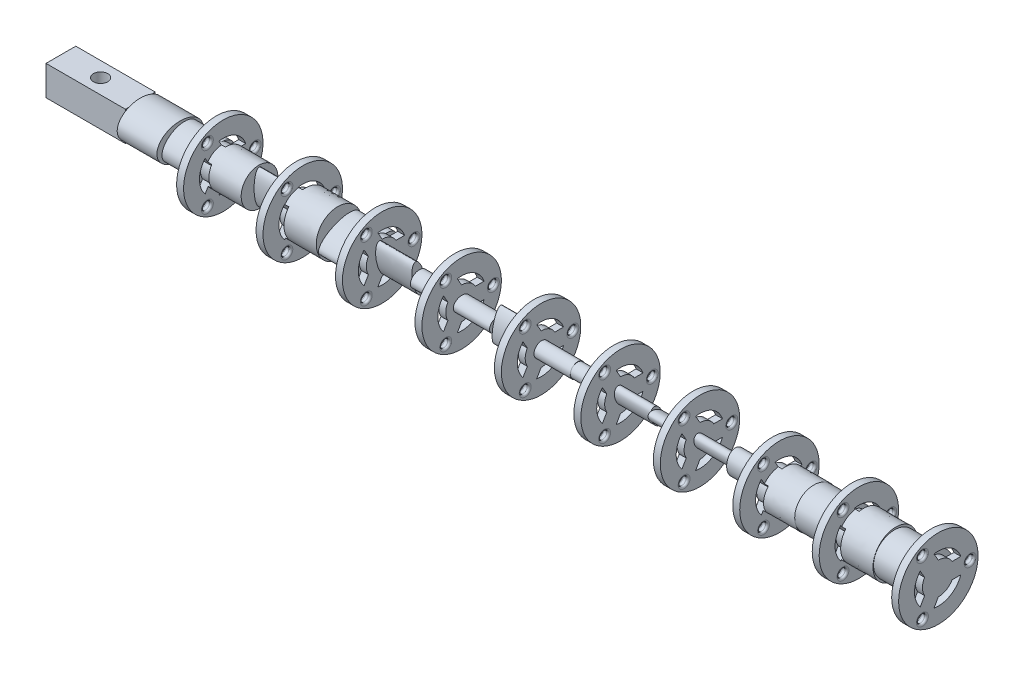
SolidWorks part; units mm, degrees
ref_plane "Front Plane" through (0, 0, 0) normal (0, 0, 1) x (1, 0, 0)
ref_plane "Top Plane" through (0, 0, 0) normal (0, 1, 0) x (1, 0, 0)
ref_plane "Right Plane" through (0, 0, 0) normal (1, 0, 0) x (0, 0, -1)
sketch "Sketch28" plane through (0, 0, 0) normal (1, 0, 0) x (0, 0, -1)
  line L0 (0, 0) -> (0, 30) construction
  line L1 (0, 0) -> (-30, 0) construction
  line L2 (19.0774, 0) -> (-19.0774, 0) construction
  dimension "D1" = 30
sketch "Sketch1" plane through (0, 0, 0) normal (1, 0, 0) x (0, 0, -1)
  line L0 (0, 4.3212) -> (0, 0) construction
  line L1 (0, 0) -> (-5.8276, 0) construction
  line L2 (0, 0) -> (0, 30) construction
  ellipse E0 centre (0, 0) end of major axis (-5.8276, 0) minor radius 4.3212
  dimension "ry_1" = 4.3212
  dimension "rz_1" = 5.8276
  dimension "phi_1" = 0
extrude "Boss-Extrude1" add sketch "Sketch1" along normal blind 10
ref_plane "Plane1" through (10, 0, 0) normal (1, 0, 0) x (0, 0, -1)
sketch "Sketch2" plane through (10, 0, 0) normal (1, 0, 0) x (0, 0, -1)
  line L0 (0, 0) -> (-1.4016, 3.0904) construction
  line L1 (0, 0) -> (-4.3308, -1.9641) construction
  line L3 (0, 0) -> (0, 30) construction
  ellipse E0 centre (0, 0) end of major axis (4.3308, 1.9641) minor radius 3.3934
  dimension "phi_2" = 24.395
  dimension "ry_2" = 3.3934
  dimension "rz_2" = 4.7554
extrude "Boss-Extrude2" add sketch "Sketch2" along normal blind 10
ref_plane "Plane2" through (20, 0, 0) normal (1, 0, 0) x (0, 0, -1)
sketch "Sketch3" plane through (20, 0, 0) normal (1, 0, 0) x (0, 0, -1)
  line L0 (0, 0) -> (-2.0467, 4.3518) construction
  line L1 (0, 0) -> (-4.1465, -1.9502) construction
  line L2 (0, 0) -> (0, 30) construction
  ellipse E0 centre (0, 0) end of major axis (-2.0467, 4.3518) minor radius 4.5822
  dimension "ry_3" = 4.809
  dimension "rz_3" = 4.5822
  dimension "phi_3" = 25.188
extrude "Boss-Extrude3" add sketch "Sketch3" along normal blind 10
ref_plane "Plane3" through (30, 0, 0) normal (1, 0, 0) x (0, 0, -1)
sketch "Sketch4" plane through (30, 0, 0) normal (1, 0, 0) x (0, 0, -1)
  line L0 (-0.0912, 4.3279) -> (0, 0) construction
  line L1 (0, 0) -> (-1.3721, -0.0289) construction
  line L2 (0, 0) -> (0, 30) construction
  ellipse E0 centre (0, 0) end of major axis (0.0912, -4.3279) minor radius 1.3724
  dimension "ry_4" = 4.3289
  dimension "rz_4" = 1.3724
  dimension "phi_4" = 1.207
extrude "Boss-Extrude4" add sketch "Sketch4" along normal blind 10
ref_plane "Plane4" through (40, 0, 0) normal (1, 0, 0) x (0, 0, -1)
sketch "Sketch5" plane through (40, 0, 0) normal (1, 0, 0) x (0, 0, -1)
  line L0 (-3.5013, 4.7623) -> (0, 0) construction
  line L1 (0, 0) -> (-4.5221, -3.3247) construction
  line L2 (0, 0) -> (0, 30) construction
  ellipse E0 centre (0, 0) end of major axis (-3.5013, 4.7623) minor radius 5.6128
  dimension "ry_5" = 5.9109
  dimension "rz_5" = 5.6128
  dimension "phi_5" = 36.324
extrude "Boss-Extrude5" add sketch "Sketch5" along normal blind 10
ref_plane "Plane5" through (50, 0, 0) normal (1, 0, 0) x (0, 0, -1)
sketch "Sketch6" plane through (50, 0, 0) normal (1, 0, 0) x (0, 0, -1)
  line L0 (-0.9096, 2.2618) -> (0, 0) construction
  line L1 (0, 0) -> (-5.0808, -2.0433) construction
  line L2 (0, 0) -> (0, 30) construction
  ellipse E0 centre (0, 0) end of major axis (-5.0808, -2.0433) minor radius 2.4378
  dimension "ry_6" = 2.4378
  dimension "rz_6" = 5.4763
  dimension "phi_6" = 21.908
extrude "Boss-Extrude6" add sketch "Sketch6" along normal blind 10
ref_plane "Plane6" through (60, 0, 0) normal (1, 0, 0) x (0, 0, -1)
sketch "Sketch7" plane through (60, 0, 0) normal (1, 0, 0) x (0, 0, -1)
  line L0 (-0.8479, 3.9653) -> (0, 0) construction
  line L1 (0, 0) -> (-1.4136, -0.3023) construction
  line L2 (0, 0) -> (0, 30) construction
  ellipse E0 centre (0, 0) end of major axis (0.8479, -3.9653) minor radius 1.4456
  dimension "ry_7" = 4.0549
  dimension "rz_7" = 1.4456
  dimension "phi_7" = 12.069
extrude "Boss-Extrude7" add sketch "Sketch7" along normal blind 10
ref_plane "Plane7" through (70, 0, 0) normal (1, 0, 0) x (0, 0, -1)
sketch "Sketch8" plane through (70, 0, 0) normal (1, 0, 0) x (0, 0, -1)
  line L0 (-0.6185, 1.5939) -> (0, 0) construction
  line L1 (0, 0) -> (-1.9484, -0.756) construction
  line L2 (0, 0) -> (0, 30) construction
  ellipse E0 centre (0, 0) end of major axis (-1.9484, -0.756) minor radius 1.7097
  dimension "ry_8" = 1.7097
  dimension "rz_8" = 2.09
  dimension "phi_8" = 21.207
extrude "Boss-Extrude8" add sketch "Sketch8" along normal blind 10
ref_plane "Plane8" through (80, 0, 0) normal (1, 0, 0) x (0, 0, -1)
sketch "Sketch9" plane through (80, 0, 0) normal (1, 0, 0) x (0, 0, -1)
  line L0 (-0.1773, 1.7176) -> (0, 0) construction
  line L1 (0, 0) -> (-2.0864, -0.2153) construction
  line L2 (0, 0) -> (0, 30) construction
  ellipse E0 centre (0, 0) end of major axis (2.0864, 0.2153) minor radius 1.7267
  dimension "ry_9" = 1.7267
  dimension "rz_9" = 2.0974
  dimension "phi_9" = 5.893
extrude "Boss-Extrude9" add sketch "Sketch9" along normal blind 10
ref_plane "Plane9" through (90, 0, 0) normal (1, 0, 0) x (0, 0, -1)
sketch "Sketch10" plane through (90, 0, 0) normal (1, 0, 0) x (0, 0, -1)
  line L0 (-1.2148, 0.2533) -> (0, 0) construction
  line L1 (0, 0) -> (-0.7981, -3.8268) construction
  line L2 (0, 0) -> (0, 30) construction
  ellipse E0 centre (0, 0) end of major axis (-0.7981, -3.8268) minor radius 1.2409
  dimension "ry_10" = 1.2409
  dimension "rz_10" = 3.9091
  dimension "phi_10" = 78.22
extrude "Boss-Extrude10" add sketch "Sketch10" along normal blind 10
ref_plane "Plane10" through (100, 0, 0) normal (1, 0, 0) x (0, 0, -1)
sketch "Sketch11" plane through (100, 0, 0) normal (1, 0, 0) x (0, 0, -1)
  line L0 (-1.2809, 1.1559) -> (0, 0) construction
  line L1 (0, 0) -> (-1.2502, -1.3855) construction
  line L2 (0, 0) -> (0, 30) construction
  ellipse E0 centre (0, 0) end of major axis (-1.2502, -1.3855) minor radius 1.7253
  dimension "ry_11" = 1.7253
  dimension "rz_11" = 1.8662
  dimension "phi_11" = 47.938
extrude "Boss-Extrude11" add sketch "Sketch11" along normal blind 10
ref_plane "Plane11" through (110, 0, 0) normal (1, 0, 0) x (0, 0, -1)
sketch "Sketch12" plane through (110, 0, 0) normal (1, 0, 0) x (0, 0, -1)
  line L0 (-0.4519, 1.6644) -> (0, 0) construction
  line L1 (0, 0) -> (-1.7077, -0.4637) construction
  line L2 (0, 0) -> (0, 30) construction
  ellipse E0 centre (0, 0) end of major axis (1.7077, 0.4637) minor radius 1.7246
  dimension "ry_12" = 1.7246
  dimension "rz_12" = 1.7695
  dimension "phi_12" = 15.191
extrude "Boss-Extrude12" add sketch "Sketch12" along normal blind 10
ref_plane "Plane12" through (120, 0, 0) normal (1, 0, 0) x (0, 0, -1)
sketch "Sketch13" plane through (120, 0, 0) normal (1, 0, 0) x (0, 0, -1)
  line L0 (-0.9033, 2.292) -> (0, 0) construction
  line L1 (0, 0) -> (-1.2574, -0.4956) construction
  line L2 (0, 0) -> (0, 30) construction
  ellipse E0 centre (0, 0) end of major axis (-0.9033, 2.292) minor radius 1.3515
  dimension "ry_13" = 2.4636
  dimension "rz_13" = 1.3515
  dimension "phi_13" = 21.51
extrude "Boss-Extrude13" add sketch "Sketch13" along normal blind 10
ref_plane "Plane13" through (130, 0, 0) normal (1, 0, 0) x (0, 0, -1)
sketch "Sketch14" plane through (130, 0, 0) normal (1, 0, 0) x (0, 0, -1)
  line L0 (-2.0836, 1.3795) -> (0, 0) construction
  line L1 (0, 0) -> (-0.7042, -1.0636) construction
  line L2 (0, 0) -> (0, 30) construction
  ellipse E0 centre (0, 0) end of major axis (-2.0836, 1.3795) minor radius 1.2756
  dimension "ry_14" = 2.4989
  dimension "rz_14" = 1.2756
  dimension "phi_14" = 56.493
extrude "Boss-Extrude14" add sketch "Sketch14" along normal blind 10
ref_plane "Plane14" through (140, 0, 0) normal (1, 0, 0) x (0, 0, -1)
sketch "Sketch15" plane through (140, 0, 0) normal (1, 0, 0) x (0, 0, -1)
  line L0 (-1.0514, 1.824) -> (0, 0) construction
  line L1 (0, 0) -> (-1.1024, -0.6354) construction
  line L2 (0, 0) -> (0, 30) construction
  ellipse E0 centre (0, 0) end of major axis (1.0514, -1.824) minor radius 1.2724
  dimension "ry_15" = 2.1053
  dimension "rz_15" = 1.2724
  dimension "phi_15" = 29.96
extrude "Boss-Extrude15" add sketch "Sketch15" along normal blind 10
ref_plane "Plane15" through (150, 0, 0) normal (1, 0, 0) x (0, 0, -1)
sketch "Sketch16" plane through (150, 0, 0) normal (1, 0, 0) x (0, 0, -1)
  line L0 (-0.5018, 3.1443) -> (0, 0) construction
  line L1 (0, 0) -> (-2.3641, -0.3773) construction
  line L3 (0, 0) -> (0, 30) construction
  ellipse E0 centre (0, 0) end of major axis (0.5018, -3.1443) minor radius 2.394
  dimension "ry_16" = 3.1841
  dimension "rz_16" = 2.394
  dimension "phi_16" = 9.067
extrude "Boss-Extrude16" add sketch "Sketch16" along normal blind 10
ref_plane "Plane16" through (160, 0, 0) normal (1, 0, 0) x (0, 0, -1)
sketch "Sketch17" plane through (160, 0, 0) normal (1, 0, 0) x (0, 0, -1)
  line L0 (-2.0662, 3.9425) -> (0, 0) construction
  line L1 (0, 0) -> (-4.5704, -2.3953) construction
  line L2 (0, 0) -> (0, 30) construction
  ellipse E0 centre (0, 0) end of major axis (4.5704, 2.3953) minor radius 4.4511
  dimension "ry_17" = 4.4511
  dimension "rz_17" = 5.16
  dimension "phi_17" = 27.658
extrude "Boss-Extrude17" add sketch "Sketch17" along normal blind 10
ref_plane "Plane17" through (170, 0, 0) normal (1, 0, 0) x (0, 0, -1)
sketch "Sketch18" plane through (170, 0, 0) normal (1, 0, 0) x (0, 0, -1)
  line L0 (-4.1845, 3.5234) -> (0, 0) construction
  line L1 (0, 0) -> (-3.2226, -3.8272) construction
  line L2 (0, 0) -> (0, 30) construction
  ellipse E0 centre (0, 0) end of major axis (4.1845, -3.5234) minor radius 5.0033
  dimension "ry_18" = 5.4703
  dimension "rz_18" = 5.0033
  dimension "phi_18" = 49.902
extrude "Boss-Extrude18" add sketch "Sketch18" along normal blind 10
ref_plane "Plane18" through (180, 0, 0) normal (1, 0, 0) x (0, 0, -1)
sketch "Sketch19" plane through (180, 0, 0) normal (1, 0, 0) x (0, 0, -1)
  line L0 (-5.0089, 2.3836) -> (0, 0) construction
  line L1 (0, 0) -> (-2.4735, -5.1978) construction
  line L2 (0, 0) -> (0, 30) construction
  ellipse E0 centre (0, 0) end of major axis (2.4735, 5.1978) minor radius 5.5471
  dimension "ry_19" = 5.5471
  dimension "rz_19" = 5.7563
  dimension "phi_19" = 64.551
extrude "Boss-Extrude19" add sketch "Sketch19" along normal blind 10
ref_plane "Plane19" through (190, 0, 0) normal (1, 0, 0) x (0, 0, -1)
sketch "Sketch20" plane through (190, 0, 0) normal (1, 0, 0) x (0, 0, -1)
  line L0 (-5.0072, 2.2353) -> (0, 0) construction
  line L1 (0, 0) -> (-2.1273, -4.7653) construction
  line L2 (0, 0) -> (0, 30) construction
  ellipse E0 centre (0, 0) end of major axis (-5.0072, 2.2353) minor radius 5.2186
  dimension "ry_20" = 5.4835
  dimension "rz_20" = 5.2186
  dimension "phi_20" = 65.944
extrude "Boss-Extrude20" add sketch "Sketch20" along normal blind 10
sketch "Sketch21" plane through (0, 0, 0) normal (0, 1, 0) x (1, 0, 0)
  line L0 (0, 0) -> (200, 0) construction
  line L1 (19.125, 0) -> (20.875, 0)
  line L2 (19.125, 0) -> (19.125, -10)
  line L3 (19.125, -10) -> (20.875, -10)
  line L4 (20.875, 0) -> (20.875, -10)
  line L5 (200, -5.4403) -> (200, 5.4403) construction
  point P6 (20, -10)
  dimension "D1" = 20
  dimension "D2" = 10
  dimension "D3" = 1.75
revolve "Revolve1" add sketch "Sketch21" angle 360 about L0
sketch "Sketch22" plane through (20.875, 0, 0) normal (1, 0, 0) x (0, 0, -1)
  line L0 (0, 0) -> (-4, 6.9282) construction
  line L1 (0, 0) -> (-4, -6.9282) construction
  line L2 (0, 0) -> (8, 0) construction
  line L3 (22, 0) -> (-22, 0) construction
  line L4 (-4.5605, 3.899) -> (-3.4641, 2)
  line L5 (-3.4641, -2) -> (-4.5605, -3.899)
  line L6 (5.6569, 2) -> (3.4641, 2)
  line L7 (0, 4) -> (-1.0964, 5.899)
  line L8 (-1.0964, -5.899) -> (0, -4)
  line L9 (3.4641, -2) -> (5.6569, -2)
  circle A0 centre (-4, 6.9282) radius 1
  circle A1 centre (-4, -6.9282) radius 1
  circle A2 centre (8, 0) radius 1
  arc A3 (-3.4641, 2) -> (-3.4641, -2) centre (0, 0) ccw
  arc A5 (-4.5605, -3.899) -> (-4.5605, 3.899) centre (0, 0) cw
  arc A7 (-1.0964, 5.899) -> (5.6569, 2) centre (0, 0) cw
  arc A8 (3.4641, 2) -> (0, 4) centre (0, 0) ccw
  arc A9 (5.6569, -2) -> (-1.0964, -5.899) centre (0, 0) cw
  arc A10 (0, -4) -> (3.4641, -2) centre (0, 0) ccw
  point P30 (0, 0)
  dimension "D4" = 2
  dimension "D7" = 6
  dimension "D9" = 4
  dimension "D1" = 120
  dimension "D2" = 120
  dimension "D3" = 8
  dimension "D5" = 2
  dimension "D6" = 2
  dimension "D8" = 3
extrude "Cut-Extrude1" cut sketch "Sketch22" against normal up to surface (1.75 mm away) from offset 1 up to face at (19.125, 1.9641, -4.3308)
fillet "Fillet2" radius 0.5 6 edges at (20.875, -6.9282, 3) (19.125, -6.9282, 5) (20.875, 6.9282, 3) (19.125, 6.9282, 5) (20.875, 0, -9) (19.125, 0, -7)
pattern_linear "LPattern1" count 10 spacing 20 along (1, 0, 0) of "Revolve1", "Cut-Extrude1", "Fillet2"
sketch "Sketch23" plane through (0, 0, 0) normal (-1, 0, 0) x (0, 0, 1)
  line L1 (-3.75, 3.75) -> (3.75, 3.75)
  line L2 (-3.75, 3.75) -> (-3.75, -3.75)
  line L3 (-3.75, -3.75) -> (3.75, -3.75)
  line L4 (3.75, 3.75) -> (3.75, -3.75)
  line L5 (-3.75, 3.75) -> (3.75, -3.75) construction
  line L6 (-3.75, -3.75) -> (3.75, 3.75) construction
  point P0 (0, 0)
  dimension "D1" = 7.5
extrude "Boss-Extrude21" add sketch "Sketch23" along normal blind 20
sketch "Sketch26" plane through (0, -3.75, 0) normal (0, -1, 0) x (-1, 0, 0)
  line L0 (20, 3.75) -> (0, 3.75) construction
  point P0 (10, 0)
  point P7 (10, 3.75)
hole_wizard "M3 Clearance Hole1" positions "Sketch26" profile "Sketch27" hole size "M3" standard "ANSI Metric" end condition up to next
sketch "Sketch27" plane through (-10, -3.75, 0) normal (1, 0, 0) x (0, 0, -1)
  line L0 (0, 0) -> (0, 7.5)
  line L1 (0, 7.5) -> (1.8, 7.5)
  line L2 (1.8, 7.5) -> (1.8, 0)
  line L5 (1.8, 0) -> (0, 0)
  line L11 (0, -6.35) -> (0, 107.95) construction
  dimension "Thru Hole Dia." = 3.6
  dimension "Thru Hole Depth" = 7.5
